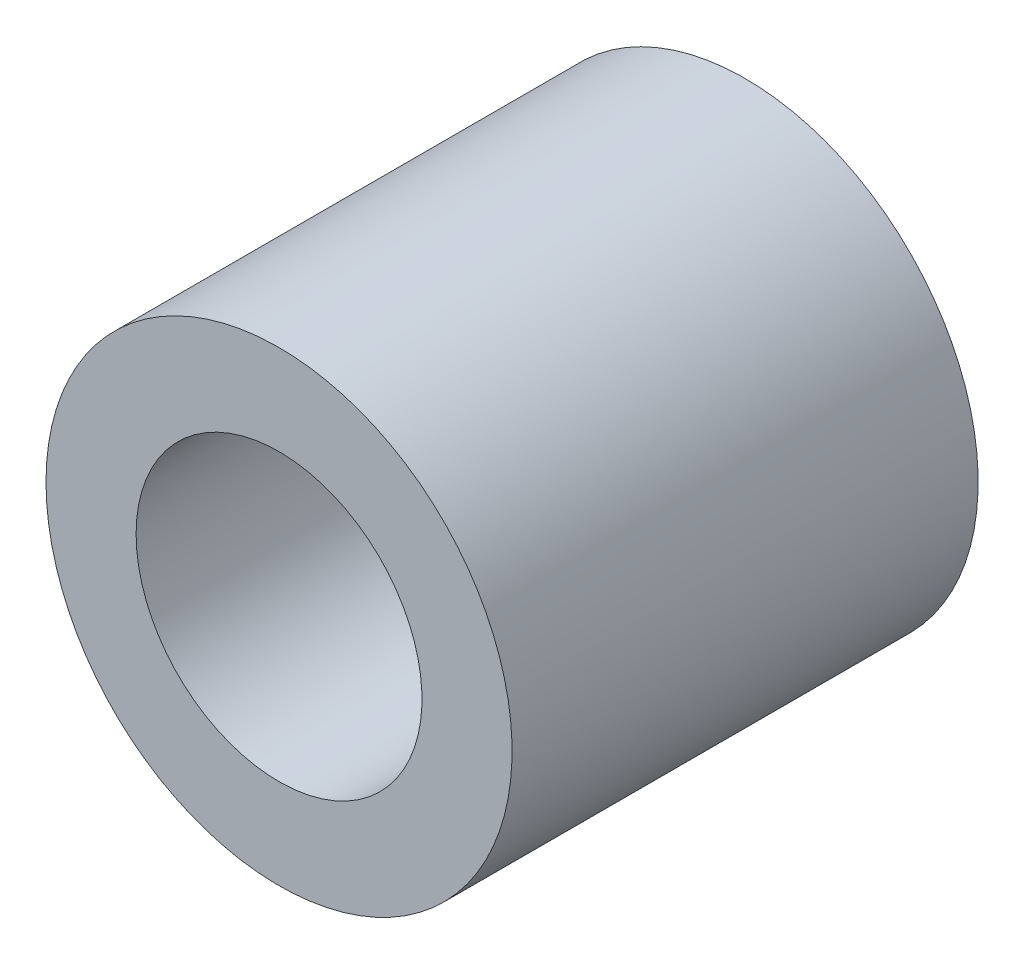
SolidWorks part; units mm, degrees
ref_plane "Front Plane" through (0, 0, 0) normal (0, 0, 1) x (1, 0, 0)
ref_plane "Top Plane" through (0, 0, 0) normal (0, 1, 0) x (1, 0, 0)
ref_plane "Right Plane" through (0, 0, 0) normal (1, 0, 0) x (0, 0, -1)
sketch "Sketch1" plane through (0, 0, 0) normal (0, 0, 1) x (1, 0, 0)
  circle A0 centre (0, 0) radius 2.3812
  circle A1 centre (0, 0) radius 1.4605
  dimension "OD" = 4.7625
  dimension "ID" = 2.921
extrude "Extrude1" add sketch "Sketch1" along normal mid plane 4.7625
sketch "Sketch2" plane through (0, 0, 0) normal (1, 0, 0) x (0, 0, -1)
  line L0 (-2.3813, -1.4605) -> (2.3812, -1.4605) construction
  line L3 (2.3812, 1.4605) -> (-2.3813, 1.4605) construction
  line L5 (-2.3813, -1.4605) -> (2.3812, -1.4605)
  line L6 (2.3812, 1.4605) -> (-2.3813, 1.4605)
sketch "Sketch4" plane through (0, 0, 2.3813) normal (0, 0, 1) x (1, 0, 0)
  line L0 (0, 0) -> (-1.0327, 1.0327)
  line L1 (0, -0.8731) -> (0, 0.8731) construction
  circle A0 centre (0, 0) radius 1.4605 construction
  dimension "D1" = 45
